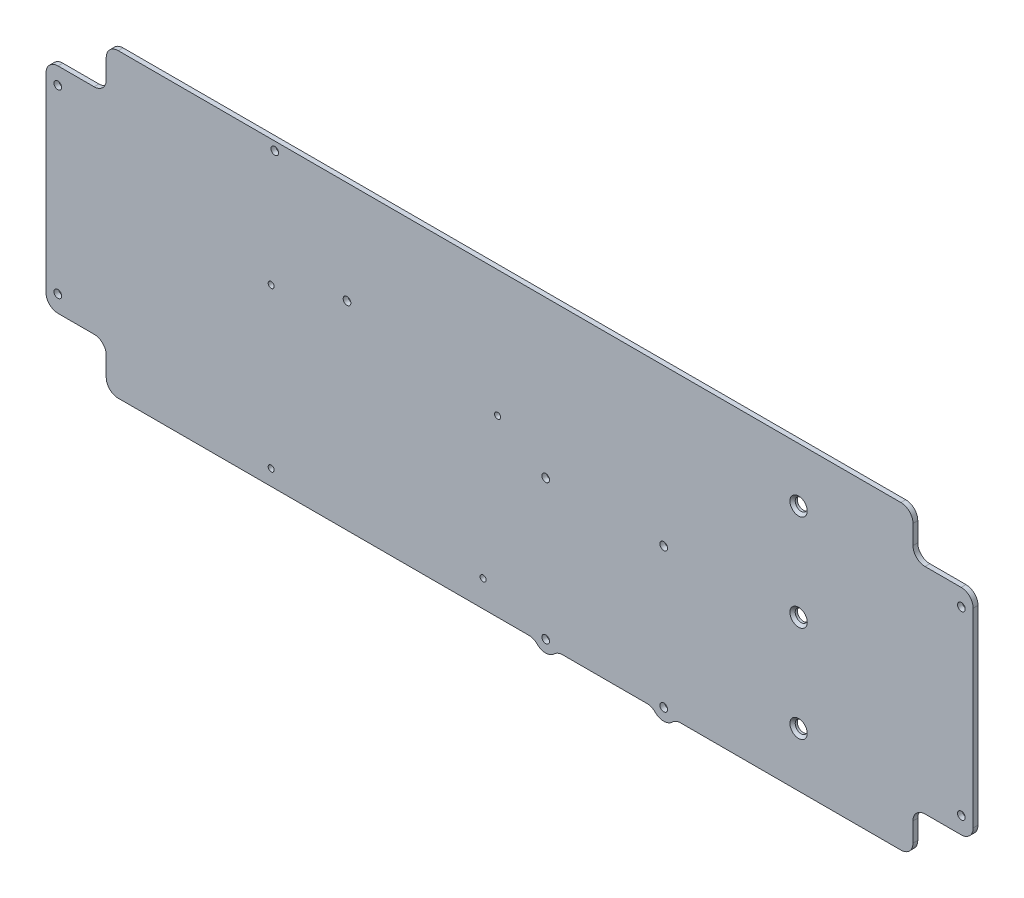
SolidWorks part; units mm, degrees
material "2014 Alloy"
ref_plane "Plan de face" through (0, 0, 0) normal (0, 0, 1) x (1, 0, 0)
ref_plane "Plan de dessus" through (0, 0, 0) normal (0, 1, 0) x (1, 0, 0)
ref_plane "Plan de droite" through (0, 0, 0) normal (1, 0, 0) x (0, 0, -1)
sketch "Sketch1" plane through (0, 0, 0) normal (0, 0, 1) x (1, 0, 0)
  line L1 (-192.5, 62.5) -> (192.5, 62.5)
  line L2 (-192.5, 62.5) -> (-192.5, -62.5)
  line L3 (-192.5, -62.5) -> (192.5, -62.5)
  line L4 (192.5, 62.5) -> (192.5, -62.5)
  line L5 (-192.5, 62.5) -> (192.5, -62.5) construction
  line L6 (-192.5, -62.5) -> (192.5, 62.5) construction
  point P0 (0, 0)
  dimension "D1" = 125
  dimension "D2" = 385
extrude "Boss-Extrude1" add sketch "Sketch1" along normal blind 2
sketch "Sketch2" plane through (0, 0, 2) normal (0, 0, 1) x (1, 0, 0)
  line L1 (-187.6, 37.5) -> (187.6, 37.5) construction
  line L2 (-187.6, 37.5) -> (-187.6, -37.5) construction
  line L3 (-187.6, -37.5) -> (187.6, -37.5) construction
  line L4 (187.6, 37.5) -> (187.6, -37.5) construction
  line L5 (-187.6, 37.5) -> (187.6, -37.5) construction
  line L6 (-187.6, -37.5) -> (187.6, 37.5) construction
  circle A0 centre (-187.6, 37.5) radius 1.6
  circle A1 centre (-187.6, -37.5) radius 1.6
  circle A2 centre (187.6, 37.5) radius 1.6
  circle A3 centre (187.6, -37.5) radius 1.6
  point P0 (0, 0)
  dimension "D1" = 75
  dimension "D2" = 375.2
extrude "Fixing_holes" cut sketch "Sketch2" against normal through all
sketch "Sketch3" plane through (0, 0, 2) normal (0, 0, 1) x (1, 0, 0)
  line L1 (-192.5, 62.5) -> (-167.5, 62.5)
  line L2 (-192.5, 62.5) -> (-192.5, 44.5)
  line L3 (-192.5, 44.5) -> (-167.5, 44.5)
  line L4 (-167.5, 62.5) -> (-167.5, 44.5)
  dimension "D1" = 18
  dimension "D2" = 25
extrude "Cut-Extrude2" cut sketch "Sketch3" against normal through all
mirror "Mirror1" about plane through (0, 0, 0) normal (0, 1, 0) of "Cut-Extrude2"
mirror "Mirror2" about plane through (0, 0, 0) normal (1, 0, 0) of "Mirror1"
sketch "Sketch4" plane through (0, 0, 2) normal (0, 0, 1) x (1, 0, 0)
  line L0 (-99, 10) -> (-5, 10) construction
  line L1 (-99, 10) -> (-99, -56) construction
  circle A0 centre (-99, 10) radius 1.25
  circle A1 centre (-99, -56) radius 1.25
  circle A2 centre (-5, 10) radius 1.25
  circle A3 centre (-11, -51.5) radius 1.25
  dimension "D4" = 66
  dimension "D5" = 94
  dimension "D7" = 61.5
  dimension "D8" = 6
  dimension "D1" = 5
  dimension "D2" = 10
extrude "Cave_board_holes" cut sketch "Sketch4" against normal through all
sketch "Sketch5" plane through (0, 0, 2) normal (0, 0, 1) x (1, 0, 0)
  line L1 (15, -2.4) -> (64, -2.4) construction
  line L2 (15, -2.4) -> (15, -60.4) construction
  line L3 (15, -60.4) -> (64, -60.4) construction
  line L4 (64, -2.4) -> (64, -60.4) construction
  circle A0 centre (15, -2.4) radius 1.6
  circle A1 centre (15, -60.4) radius 1.6
  circle A2 centre (64, -2.4) radius 1.6
  circle A3 centre (64, -60.4) radius 1.6
  dimension "D1" = 58
  dimension "D2" = 49
  dimension "D3" = 15
  dimension "D4" = 2.4
extrude "RPi_holes" cut sketch "Sketch5" against normal through all
sketch "Sketch6" plane through (0, 0, 2) normal (0, 0, 1) x (1, 0, 0)
  line L1 (-97.5, 59) -> (-67.5, 59) construction
  line L2 (-97.5, 59) -> (-97.5, 20) construction
  line L3 (-97.5, 20) -> (-67.5, 20) construction
  line L4 (-67.5, 59) -> (-67.5, 20) construction
  circle A0 centre (-97.5, 59) radius 1.6
  circle A3 centre (-67.5, 20) radius 1.6
  dimension "D1" = 39
  dimension "D2" = 30
  dimension "D3" = 67.5
  dimension "D4" = 20
extrude "buzzer_holes" cut sketch "Sketch6" against normal through all
sketch "Sketch7" plane through (0, 0, 2) normal (0, 0, 1) x (1, 0, 0)
  line L0 (0, 0) -> (178.5314, 0) construction
  circle A0 centre (120, 0) radius 2.5
  circle A1 centre (120, 40) radius 2.5
  circle A2 centre (120, -40) radius 2.5
  dimension "D4" = 120
  dimension "D5" = 40
hole_wizard "CSK for M5 Countersunk Flat Head Screw1" positions "Sketch11" profile "Sketch10" countersink size "M5" standard "ISO" end condition through all
sketch "Sketch11" plane through (0, 0, 2) normal (0, 0, 1) x (1, 0, 0)
  point P0 (120, 40)
  point P3 (120, 0)
  point P6 (120, -40)
sketch "Sketch10" plane through (120, 40, 2) normal (1, 0, 0) x (0, -1, 0)
  line L0 (0, 0) -> (0, 2)
  line L1 (0, 2) -> (2.5, 2)
  line L2 (2.5, 2) -> (2.5, 1.1)
  line L3 (2.5, 1.1) -> (3.6, 0)
  line L5 (3.6, 0) -> (0, 0)
  line L6 (-2.5, 1.1) -> (-3.6, 0) construction
  line L11 (0, -6.35) -> (0, 107.95) construction
  dimension "Thru Hole Dia." = 5
  dimension "Thru Hole Depth" = 2
  dimension "Near C'Sink Dia." = 7.2
  dimension "Near C'Sink Angle" = 90
sketch "Sketch8" plane through (0, 0, 2) normal (0, 0, 1) x (1, 0, 0)
  line L0 (-167.5, -62.5) -> (167.5, -62.5) construction
  line L2 (10.4624, -62.5) -> (19.5376, -62.5)
  line L3 (59.4624, -62.5) -> (68.5376, -62.5)
  arc A0 (10.4624, -62.5) -> (19.5376, -62.5) centre (15, -60.4) ccw
  arc A1 (59.4624, -62.5) -> (68.5376, -62.5) centre (64, -60.4) ccw
  dimension "D1" = 10
  dimension "D2" = 10
extrude "Boss-Extrude2" add sketch "Sketch8" against normal up to surface (2 mm away) up to face at (122.5, 40, 0)
fillet "Fillet1" radius 5 16 edges at (68.5376, -62.5, 1) (59.4624, -62.5, 1) (19.5376, -62.5, 1) (10.4624, -62.5, 1) (-192.5, 44.5, 1) (-167.5, 44.5, 1) (-167.5, 62.5, 1) (-167.5, -62.5, 1) (-167.5, -44.5, 1) (-192.5, -44.5, 1) (167.5, -62.5, 1) (167.5, -44.5, 1) (192.5, -44.5, 1) (192.5, 44.5, 1) (167.5, 44.5, 1) (167.5, 62.5, 1)
sketch "Sketch9" plane through (0, 0, 2) normal (0, 0, 1) x (1, 0, 0)
  line L0 (-192.5, 39.5) -> (-192.5, -39.5) construction
  line L1 (-162.5, -62.5) -> (7.958, -62.5) construction
  point P0 (-192.5, -62.5)
